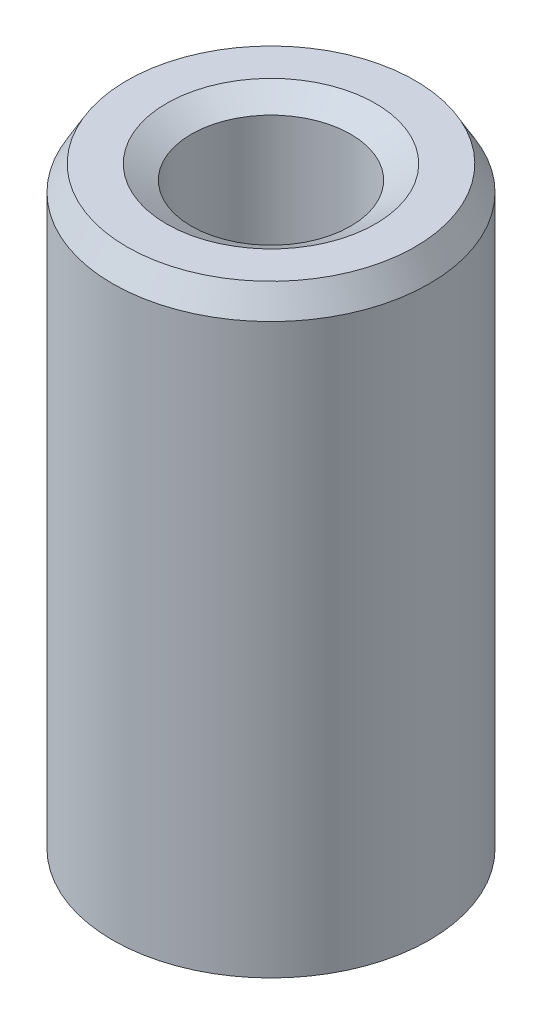
SolidWorks part; units mm, degrees
ref_plane "Front Plane" through (0, 0, 0) normal (0, 0, 1) x (1, 0, 0)
ref_plane "Top Plane" through (0, 0, 0) normal (0, 1, 0) x (1, 0, 0)
ref_plane "Right Plane" through (0, 0, 0) normal (1, 0, 0) x (0, 0, -1)
sketch "Sketch1" plane through (0, 0, 0) normal (0, 1, 0) x (1, 0, 0)
  circle A0 centre (0, 0) radius 25
  dimension "SLEEVE_OD" = 50
extrude "Boss-Extrude1" add sketch "Sketch1" along normal blind 95.8757
sketch "Sketch2" plane through (0, 0, 0) normal (0, 1, 0) x (1, 0, 0)
  circle A0 centre (0, 0) radius 12.5782
  dimension "BORE_D" = 25.1564
extrude "Cut-Extrude1" cut sketch "Sketch2" along normal through all
chamfer "Chamfer1" distance 3.9084 angle 30 4 edges at (0, 95.8757, 12.5782) (0, 0, 12.5782) (0, 0, 25) (0, 95.8757, 25) first distance on face at (0, 95.8757, 12.5782) first distance on face at (0, 0, 12.5782) first distance on face at (0, 95.8757, 25)
